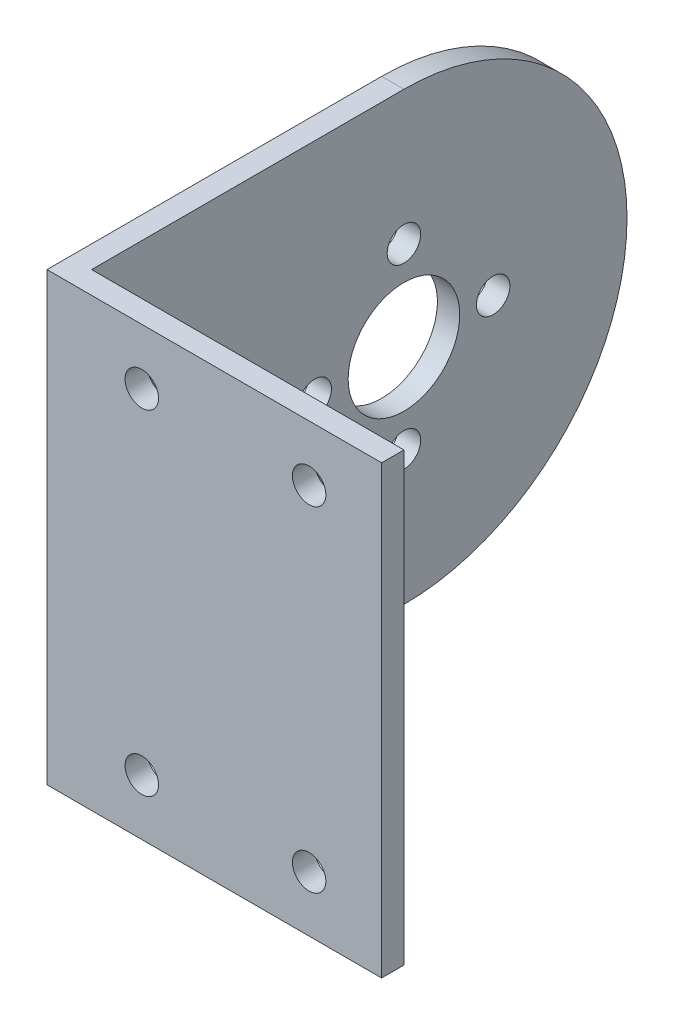
SolidWorks part; units mm, degrees
ref_plane "前视基准面" through (0, 0, 0) normal (0, 0, 1) x (1, 0, 0)
ref_plane "上视基准面" through (0, 0, 0) normal (0, 1, 0) x (1, 0, 0)
ref_plane "右视基准面" through (0, 0, 0) normal (1, 0, 0) x (0, 0, -1)
other "Configuration Table"
sketch "草图1" plane through (0, 0, 0) normal (0, 1, 0) x (1, 0, 0)
  line L0 (-2.4885, -6.0323) -> (-32.4885, -6.0323)
  line L1 (-32.4885, -6.0323) -> (-32.4885, 43.9677)
  line L2 (-32.4885, 43.9677) -> (-30.4885, 43.9677)
  line L3 (-30.4885, 43.9677) -> (-30.4885, -4.0323)
  line L4 (-30.4885, -4.0323) -> (-2.4885, -4.0323)
  line L5 (-2.4885, -4.0323) -> (-2.4885, -6.0323)
  dimension "D1" = 50
  dimension "D2" = 30
  dimension "D3" = 2
  dimension "D4" = 2
extrude "凸台-拉伸1" add sketch "草图1" along normal blind 40 contours L3 L4 L5 L0 L1 L2
fillet "圆角1" radius 20 2 edges at (-31.4885, 40, -43.9677) (-31.4885, 0, -43.9677)
sketch "草图3" plane through (-32.4885, 0, 0) normal (-1, 0, 0) x (0, 0, 1)
  circle A0 centre (-23.9677, 20) radius 5
  dimension "D1" = 10
extrude "切除-拉伸1" cut sketch "草图3" against normal blind 10 contours A0
extrude "切除-拉伸2" cut sketch "草图15" against normal blind 10
sketch "草图15" plane through (-32.4885, 20.4489, -1043.9677) normal (-1, 0, 0) x (0, 0, 1)
  circle A0 centre (1012, -0.4489) radius 1.5
  circle A1 centre (1020, 7.5511) radius 1.5
  circle A2 centre (1028, -0.4489) radius 1.5
  circle A3 centre (1020, -8.4489) radius 1.5
  point P14 (1020, -0.4489)
ref_plane "基准面1" through (-2.4885, 40, 4.0323) normal (1, 0, 0) x (0, 0, -1)
sketch "草图18" plane through (0, 0, 4.0323) normal (0, 0, -1) x (-1, 0, 0)
  line L0 (16.4885, 20) -> (16.4885, 40) construction
  line L5 (23.9885, 5) -> (8.9885, 5) construction
  line L6 (23.9885, 5) -> (23.9885, 35) construction
  line L7 (23.9885, 35) -> (8.9885, 35) construction
  line L8 (8.9885, 5) -> (8.9885, 35) construction
  line L9 (23.9885, 5) -> (8.9885, 35) construction
  line L10 (23.9885, 35) -> (8.9885, 5) construction
  line L11 (2.4885, 40) -> (32.4885, 40) construction
  line L12 (16.4885, 40) -> (16.4885, 0) construction
  circle A0 centre (8.9885, 35) radius 1.5
  circle A1 centre (23.9885, 35) radius 1.5
  circle A2 centre (23.9885, 5) radius 1.5
  circle A3 centre (8.9885, 5) radius 1.5
  point P0 (16.4885, 20)
  dimension "D3" = 3
  dimension "D1" = 15
  dimension "D2" = 30
extrude "切除-拉伸5" cut sketch "草图18" against normal blind 10
